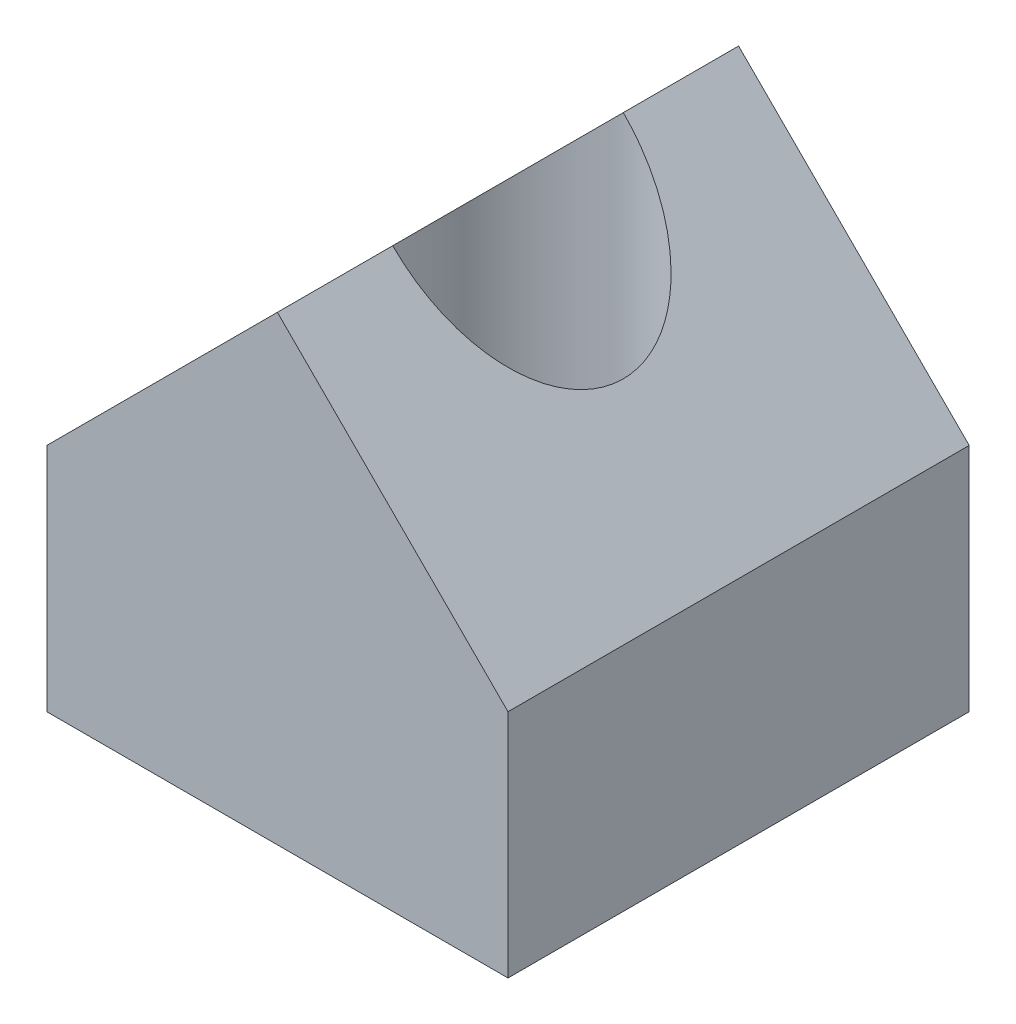
SolidWorks part; units mm, degrees
material "6061-T6 (SS)"
ref_plane "Front Plane" through (0, 0, 0) normal (0, 0, 1) x (1, 0, 0)
ref_plane "Top Plane" through (0, 0, 0) normal (0, 1, 0) x (1, 0, 0)
ref_plane "Right Plane" through (0, 0, 0) normal (1, 0, 0) x (0, 0, -1)
sketch "Sketch1" plane through (0, 0, 0) normal (0, 0, 1) x (1, 0, 0)
  line L0 (0, 6.35) -> (6.35, 0)
  line L1 (-6.35, -6.35) -> (6.35, -6.35)
  line L2 (-6.35, -6.35) -> (-6.35, 6.35)
  line L3 (-6.35, 6.35) -> (6.35, 6.35)
  line L4 (6.35, -6.35) -> (6.35, 6.35)
  line L5 (-6.35, -6.35) -> (6.35, 6.35) construction
  line L6 (-6.35, 6.35) -> (6.35, -6.35) construction
  line L7 (0, 6.35) -> (-6.35, 0)
  point P0 (0, 0)
  point P8 (-6.35, 0)
  point P10 (0, 0)
  point P11 (0, 0)
  point P12 (6.4693, -1.7068)
  point P13 (0, 0)
  dimension "D1" = 12.7
  dimension "D2" = 12.7
  dimension "D3" = 90
  dimension "D4" = 45
extrude "Boss-Extrude1" add sketch "Sketch1" along normal blind 12.7 contours L0 L7 L2 L1 L4 region at (0, -1.4111, 0)
sketch "Sketch2" plane through (0, -6.35, 0) normal (0, -1, 0) x (1, 0, 0)
  line L0 (0, 0) -> (0, 12.7) construction
  circle A0 centre (0, 6.35) radius 3.175
  dimension "D1" = 6.35
extrude ".25-20 tapped hole" cut sketch "Sketch2" against normal through all
